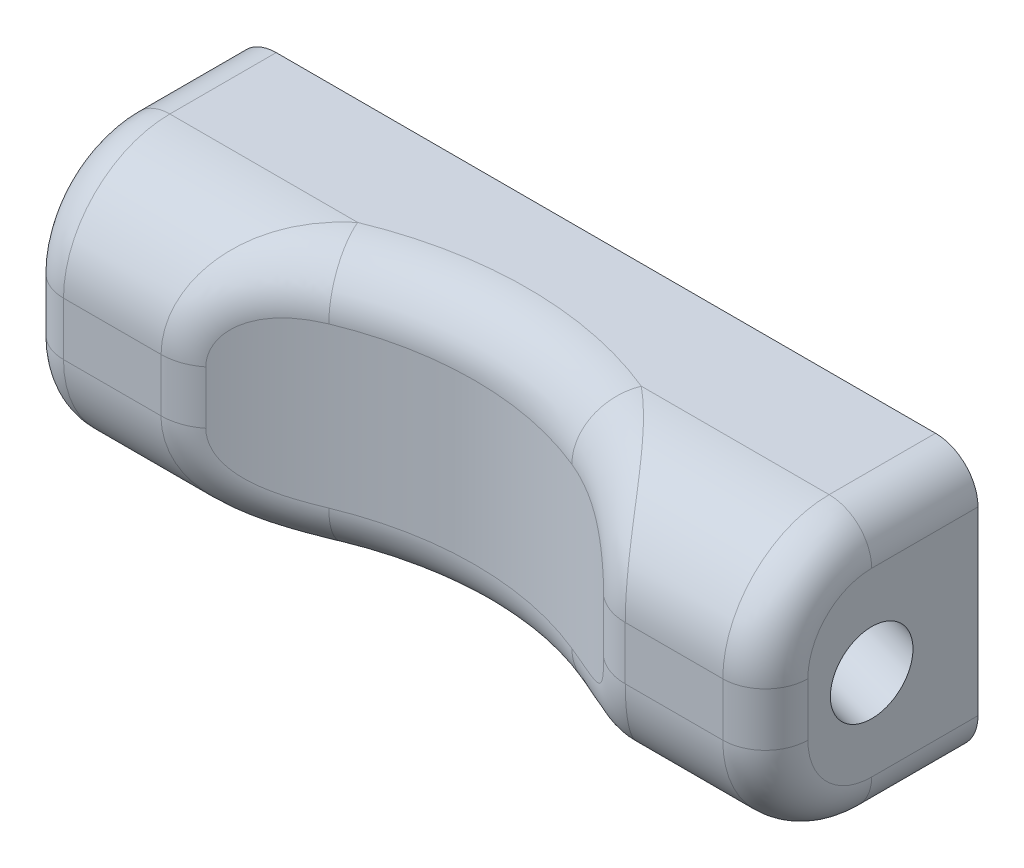
SolidWorks part; units mm, degrees
ref_plane "Front Plane" through (0, 0, 0) normal (0, 0, 1) x (1, 0, 0)
ref_plane "Top Plane" through (0, 0, 0) normal (0, 1, 0) x (1, 0, 0)
ref_plane "Right Plane" through (0, 0, 0) normal (1, 0, 0) x (0, 0, -1)
sketch "Sketch1" plane through (0, 0, 0) normal (0, 0, 1) x (1, 0, 0)
  line L0 (68.5859, -300) -> (68.5859, 538.7259) construction
  line L1 (33.5859, 8.7259) -> (103.5859, 8.7259)
  line L2 (33.5859, 8.7259) -> (33.5859, -16.2741)
  line L3 (33.5859, -16.2741) -> (103.5859, -16.2741)
  line L4 (103.5859, 8.7259) -> (103.5859, -16.2741)
  dimension "D1" = 530
  dimension "D2" = 25
  dimension "D3" = 70
  dimension "D4" = 35
extrude "Boss-Extrude1" add sketch "Sketch1" along normal blind 20
ref_plane "Plane1" through (0, -3.7741, 0) normal (0, 1, 0) x (1, 0, 0)
sketch "Sketch3" plane through (0, -3.7741, 0) normal (0, 1, 0) x (1, 0, 0)
  line L0 (68.5859, 0) -> (68.5859, -20) construction
  line L1 (103.5859, 0) -> (33.5859, 0) construction
  line L2 (103.5859, -20) -> (33.5859, -20) construction
  line L3 (68.5859, 0) -> (103.5859, -9.3782)
  line L5 (103.5859, -20) -> (103.5859, 0) construction
  dimension "D1" = 105
ref_plane "Plane2" through (103.5859, -3.7741, 9.3782) normal (0.9659, 0, 0.2588) x (0.2588, 0, -0.9659)
sketch "Sketch4" plane through (103.5859, -3.7741, 9.3782) normal (0.9659, 0, 0.2588) x (0.2588, 0, -0.9659)
  circle A0 centre (-0.6006, 0) radius 3.75
extrude "Cut-Extrude1" cut sketch "Sketch4" against normal blind 20 and the other way through all
ref_plane "Plane3" through (68.5859, 0, 0) normal (1, 0, 0) x (0, 0, -1)
mirror "Mirror1" about plane through (68.5859, 0, 0) normal (1, 0, 0) of "Cut-Extrude1"
fillet "Fillet1" radius 10 2 edges at (68.5859, -16.2741, 20) (68.5859, 8.7259, 20)
sketch "Sketch5" plane through (0, 8.7259, 0) normal (0, 1, 0) x (1, 0, 0)
  line L0 (68.5859, 0) -> (68.5859, -20) construction
  line L1 (103.5859, 0) -> (33.5859, 0) construction
  line L2 (103.5859, -20) -> (33.5859, -20) construction
  line L3 (48.5859, -20) -> (88.5859, -20)
  arc A0 (48.5859, -20) -> (88.5859, -20) centre (68.5859, -42.3607) cw
  dimension "D3" = 30
  dimension "D1" = 20
  dimension "D2" = 20
extrude "Cut-Extrude2" cut sketch "Sketch5" against normal through all
fillet "Fillet2" radius 5 4 edges at (88.5859, -3.7741, 20) (71.7578, -15.9491, 12.5288) (48.5859, -3.7741, 20) (65.414, 8.4009, 12.5288)
fillet "Fillet3" radius 4 10 edges at (33.5859, -16.2741, 5) (33.5859, -13.3452, 17.0711) (33.5859, -3.7741, 20) (33.5859, 8.7259, 5) (103.5859, 8.7259, 5) (103.5859, -16.2741, 5) (103.5859, -13.3452, 17.0711) (103.5859, -3.7741, 20) (33.5859, 5.797, 17.0711) (103.5859, 5.797, 17.0711)
